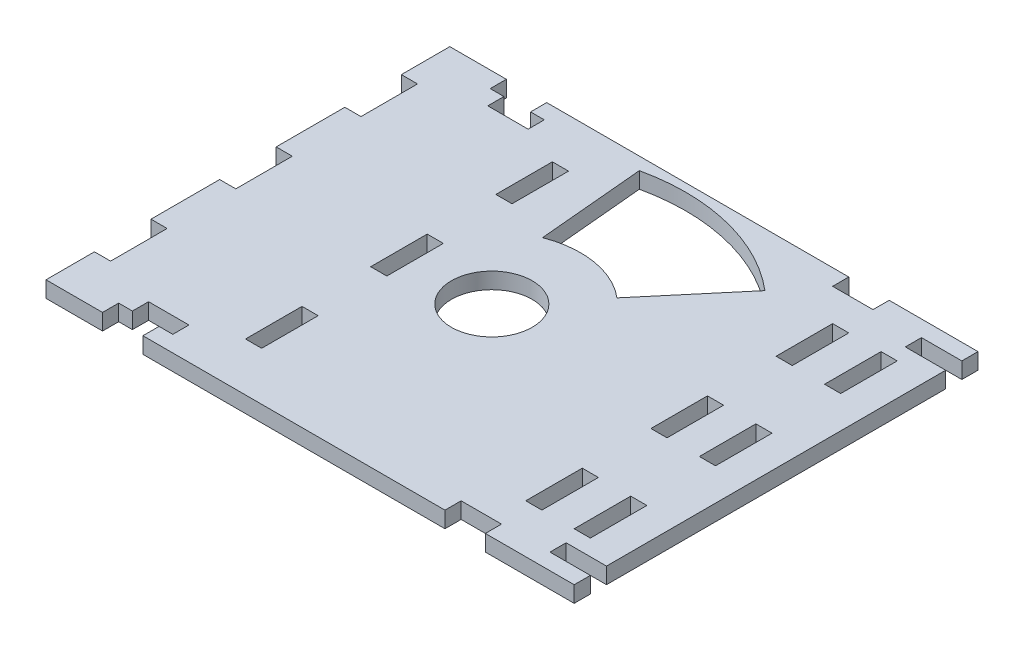
SolidWorks part; units mm, degrees
ref_plane "Front Plane" through (0, 0, 0) normal (0, 0, 1) x (1, 0, 0)
ref_plane "Top Plane" through (0, 0, 0) normal (0, 1, 0) x (1, 0, 0)
ref_plane "Right Plane" through (0, 0, 0) normal (1, 0, 0) x (0, 0, -1)
sketch "Sketch2" plane through (0, 0, 0) normal (0, 1, 0) x (1, 0, 0)
  line L1 (-50, 25) -> (50, 25)
  line L2 (-50, 25) -> (-50, -25)
  line L3 (-50, -25) -> (50, -25)
  line L4 (50, 25) -> (50, -25)
  line L5 (-50, 25) -> (50, -25) construction
  line L6 (-50, -25) -> (50, 25) construction
  circle A0 centre (0, 0) radius 5
  point P0 (0, 0)
  dimension "D3" = 10
  dimension "D1" = 100
  dimension "D2" = 50
extrude "Boss-Extrude1" add sketch "Sketch2" along normal blind 2
sketch "Sketch5" plane through (0, 0, 0) normal (0, -1, 0) x (-1, 0, 0)
  line L0 (-50, 25) -> (50, 25) construction
  line L1 (-23.2, -19) -> (-25.2, -19)
  line L2 (-23.2, -19) -> (-23.2, -12)
  line L3 (-23.2, -12) -> (-25.2, -12)
  line L4 (-25.2, -19) -> (-25.2, -12)
  line L5 (-23.2, -3.5) -> (-25.2, -3.5)
  line L6 (-23.2, -3.5) -> (-23.2, 3.5)
  line L7 (-23.2, 3.5) -> (-25.2, 3.5)
  line L8 (-25.2, -3.5) -> (-25.2, 3.5)
  line L9 (-23.2, 12) -> (-25.2, 12)
  line L10 (-23.2, 12) -> (-23.2, 19)
  line L11 (-23.2, 19) -> (-25.2, 19)
  line L12 (-25.2, 12) -> (-25.2, 19)
  line L13 (11.5, 12) -> (9.5, 12)
  line L14 (11.5, 12) -> (11.5, 19)
  line L15 (11.5, 19) -> (9.5, 19)
  line L16 (9.5, 12) -> (9.5, 19)
  line L17 (11.5, -3.5) -> (9.5, -3.5)
  line L18 (11.5, -3.5) -> (11.5, 3.5)
  line L19 (11.5, 3.5) -> (9.5, 3.5)
  line L20 (9.5, -3.5) -> (9.5, 3.5)
  line L21 (11.5, -19) -> (9.5, -19)
  line L22 (11.5, -19) -> (11.5, -12)
  line L23 (11.5, -12) -> (9.5, -12)
  line L24 (9.5, -19) -> (9.5, -12)
  line L25 (50, -25) -> (-50, -25) construction
  line L26 (-50, 25) -> (50, 25) construction
  line L27 (50, -25) -> (-50, -25) construction
  point P29 (-24.2, -19)
  dimension "D1" = 2
  dimension "D2" = 7
  dimension "D3" = 7
  dimension "D4" = 7
  dimension "D5" = 2
  dimension "D6" = 2
  dimension "D7" = 2
  dimension "D8" = 2
  dimension "D9" = 2
  dimension "D10" = 7
  dimension "D11" = 7
  dimension "D12" = 7
  dimension "D13" = 6
  dimension "D14" = 8.5
  dimension "D15" = 8.5
  dimension "D16" = 6
  dimension "D17" = 6
  dimension "D18" = 8.5
  dimension "D19" = 8.5
  dimension "D20" = 6
  dimension "D21" = 9.5
  dimension "D22" = 0
  dimension "D23" = 32.7
  dimension "D24" = 0
  dimension "D25" = 0
  dimension "D26" = 0
  dimension "D27" = 32.7
extrude "Cut-Extrude3" cut sketch "Sketch5" against normal blind 2
sketch "Sketch10" plane through (0, 2, 0) normal (0, 1, 0) x (1, 0, 0)
  line L0 (-5.1716, 23.4362) -> (-3.9753, 10.2565)
  line L1 (15.4739, 18.3455) -> (7.0922, 8.4084)
  arc A0 (-3.9753, 10.2565) -> (7.0922, 8.4084) centre (0, 0) cw
  arc A1 (-5.1716, 23.4362) -> (15.4739, 18.3455) centre (0, 0) cw
  dimension "D1" = 24
  dimension "D2" = 11
extrude "Cut-Extrude6" cut sketch "Sketch10" against normal blind 2 contours A1 L0 A0 L1 region at (3.832, 2, -17.0402)
sketch "Sketch11" plane through (0, 2, 0) normal (0, 1, 0) x (1, 0, 0)
  line L0 (-50, -25) -> (50, -25) construction
  line L1 (-21.5, -25) -> (-16.5, -25)
  line L2 (-21.5, -25) -> (-21.5, -23)
  line L3 (-21.5, -23) -> (-16.5, -23)
  line L4 (-16.5, -25) -> (-16.5, -23)
  line L5 (50, 25) -> (-50, 25) construction
  line L6 (35.2, -25) -> (30.2, -25)
  line L7 (35.2, -25) -> (35.2, -23)
  line L8 (35.2, -23) -> (30.2, -23)
  line L9 (30.2, -25) -> (30.2, -23)
  line L10 (35.2, 25) -> (30.2, 25)
  line L11 (35.2, 25) -> (35.2, 23)
  line L12 (35.2, 23) -> (30.2, 23)
  line L13 (30.2, 25) -> (30.2, 23)
  line L15 (-21.5, 25) -> (-16.5, 25)
  line L16 (-21.5, 25) -> (-21.5, 23)
  line L17 (-21.5, 23) -> (-16.5, 23)
  line L18 (-16.5, 25) -> (-16.5, 23)
  line L19 (35.2, 23) -> (30.2, 23)
  line L20 (35.2, 23) -> (35.2, 21)
  line L21 (35.2, 21) -> (30.2, 21)
  line L22 (30.2, 23) -> (30.2, 21)
  line L23 (-16.5, 23) -> (-21.5, 23)
  line L24 (-16.5, 23) -> (-16.5, 21)
  line L25 (-16.5, 21) -> (-21.5, 21)
  line L26 (-21.5, 23) -> (-21.5, 21)
  line L27 (-16.5, -23) -> (-21.5, -23)
  line L28 (-16.5, -23) -> (-16.5, -21)
  line L29 (-16.5, -21) -> (-21.5, -21)
  line L30 (-21.5, -23) -> (-21.5, -21)
  line L31 (35.2, -23) -> (30.2, -23)
  line L32 (35.2, -23) -> (35.2, -21)
  line L33 (35.2, -21) -> (30.2, -21)
  line L34 (30.2, -23) -> (30.2, -21)
  dimension "D1" = 2
  dimension "D2" = 2
  dimension "D3" = 2
  dimension "D4" = 2
  dimension "D5" = 5
  dimension "D6" = 5
  dimension "D7" = 5
  dimension "D8" = 5
  dimension "D9" = 5
  dimension "D10" = 5
  dimension "D11" = 5
  dimension "D12" = 5
  dimension "D13" = 2
  dimension "D14" = 2
  dimension "D15" = 2
  dimension "D16" = 2
extrude "Cut-Extrude7" cut sketch "Sketch11" against normal blind 2 contours L12 L22 L21 L20 | L17 L26 L25 L24 | L30 L3 L28 L29 | L34 L8 L32 L33 region at (-19, 2, 22) region at (32.7, 2, 22) region at (32.7, 2, -22) region at (-19, 2, -22)
sketch "Sketch12" plane through (0, 2, 0) normal (0, 1, 0) x (1, 0, 0)
  line L0 (-50, -25) -> (50, -25) construction
  line L1 (-43.5, -25) -> (-50, -25)
  line L2 (-43.5, -25) -> (-43.5, 25)
  line L3 (-43.5, 25) -> (-50, 25)
  line L4 (-50, -25) -> (-50, 25)
  line L5 (-50, -25) -> (50, -25) construction
  line L6 (47.2, -25) -> (50, -25)
  line L7 (47.2, -25) -> (47.2, 25)
  line L8 (47.2, 25) -> (50, 25)
  line L9 (50, -25) -> (50, 25)
  line L11 (35.2, 23) -> (35.2, 21) construction
  line L12 (-21.5, 23) -> (-21.5, 21) construction
  dimension "D1" = 12
  dimension "D2" = 22
extrude "Cut-Extrude8" cut sketch "Sketch12" against normal blind 6
sketch "Sketch13" plane through (0, 2, 0) normal (0, 1, 0) x (1, 0, 0)
  line L0 (35.2, 25) -> (35.2, -25)
  line L1 (-28.2, 19) -> (-30.2, 19)
  line L2 (-28.2, 19) -> (-28.2, 12)
  line L3 (-28.2, 12) -> (-30.2, 12)
  line L4 (-30.2, 19) -> (-30.2, 12)
  line L5 (-28.2, 3.5) -> (-30.2, 3.5)
  line L6 (-28.2, 3.5) -> (-28.2, -3.5)
  line L7 (-28.2, -3.5) -> (-30.2, -3.5)
  line L8 (-30.2, 3.5) -> (-30.2, -3.5)
  line L9 (-28.2, -12) -> (-30.2, -12)
  line L10 (-28.2, -12) -> (-28.2, -19)
  line L11 (-28.2, -19) -> (-30.2, -19)
  line L12 (-30.2, -12) -> (-30.2, -19)
  line L13 (29.2, 19) -> (31.2, 19)
  line L14 (29.2, 19) -> (29.2, 12)
  line L15 (29.2, 12) -> (31.2, 12)
  line L16 (31.2, 19) -> (31.2, 12)
  line L17 (29.2, 3.5) -> (31.2, 3.5)
  line L18 (29.2, 3.5) -> (29.2, -3.5)
  line L19 (29.2, -3.5) -> (31.2, -3.5)
  line L20 (31.2, 3.5) -> (31.2, -3.5)
  line L21 (29.2, -12) -> (31.2, -12)
  line L22 (29.2, -12) -> (29.2, -19)
  line L23 (29.2, -19) -> (31.2, -19)
  line L24 (31.2, -12) -> (31.2, -19)
  line L26 (47.2, 25) -> (-43.5, 25) construction
  line L27 (47.2, 25) -> (-43.5, 25) construction
  line L28 (-43.5, -25) -> (47.2, -25) construction
  line L29 (47.2, 25) -> (-43.5, 25) construction
  line L30 (-43.5, -25) -> (47.2, -25) construction
  line L31 (-43.5, -25) -> (-30.2, -25)
  line L32 (-43.5, -25) -> (-43.5, 25)
  line L33 (-43.5, 25) -> (-30.2, 25)
  line L34 (-30.2, -25) -> (-30.2, 25)
  line L35 (47.2, -25) -> (31.2, -25)
  line L36 (47.2, -25) -> (47.2, 25)
  line L37 (47.2, 25) -> (31.2, 25)
  line L38 (31.2, -25) -> (31.2, 25)
  line L39 (24.2, -25) -> (19.2, -25)
  line L40 (24.2, -25) -> (24.2, -23)
  line L41 (24.2, -23) -> (19.2, -23)
  line L42 (19.2, -25) -> (19.2, -23)
  line L43 (24.2, 23) -> (19.2, 23)
  line L44 (24.2, 23) -> (24.2, 25)
  line L45 (24.2, 25) -> (19.2, 25)
  line L46 (19.2, 23) -> (19.2, 25)
  line L48 (-23.2, 25) -> (-18.2, 25)
  line L49 (-23.2, 25) -> (-23.2, 23)
  line L50 (-23.2, 23) -> (-18.2, 23)
  line L51 (-18.2, 25) -> (-18.2, 23)
  line L52 (-23.2, -25) -> (-18.2, -25)
  line L53 (-23.2, -25) -> (-23.2, -23)
  line L54 (-23.2, -23) -> (-18.2, -23)
  line L55 (-18.2, -25) -> (-18.2, -23)
  point P30 (30.2, 3.5)
  point P47 (28.637, 23.1685)
  line M32 (47.2, -25) -> (47.2, 25)
  line M39 (-21.5, 23) -> (-16.5, 23)
  line M41 (47.2, 25) -> (-43.5, 25)
  line M42 (-43.5, 25) -> (-43.5, -25)
  line M45 (-16.5, -23) -> (-21.5, -23)
  line M47 (-43.5, -25) -> (47.2, -25)
  line M120 (35.2, 23) -> (35.2, 21)
  line M125 (35.2, -21) -> (35.2, -23)
  dimension "D1" = 2
  dimension "D2" = 2
  dimension "D3" = 2
  dimension "D4" = 2
  dimension "D5" = 2
  dimension "D6" = 2
  dimension "D7" = 57.4
  dimension "D8" = 57.4
  dimension "D9" = 57.4
  dimension "D10" = 7
  dimension "D11" = 7
  dimension "D12" = 7
  dimension "D13" = 7
  dimension "D14" = 7
  dimension "D15" = 7
  dimension "D16" = 5
  dimension "D17" = 5
  dimension "D18" = 5
  dimension "D19" = 6
  dimension "D20" = 8.5
  dimension "D21" = 8.5
  dimension "D22" = 6
  dimension "D23" = 6
  dimension "D24" = 8.5
  dimension "D25" = 8.5
  dimension "D26" = 6
  dimension "D27" = 5
  dimension "D28" = 2
  dimension "D29" = 2
  dimension "D30" = 2
  dimension "D31" = 2
  dimension "D32" = 5
  dimension "D33" = 5
  dimension "D34" = 5
  dimension "D35" = 5
extrude "Cut-Extrude10" cut sketch "Sketch13" against normal blind 6 contours L0 M41 M120 M125 M47 M32 | L42 L40 L41 M47 | L24 L21 L22 L23 | L20 L17 L18 L19 | L16 L13 L14 L15 | L51 L49 L50 M41 M39 | L55 L54 L53 M47 M45 | L5 L8 L7 L6 | L1 L4 L3 L2 | L34 L12 L8 L4 M47 M41 M42 | L45 L46 L43 L44 | L10 L11 L12 L9 region at (41.2, 2, 0) region at (30.2, 2, -15.5) region at (30.2, 2, 0) region at (-20.7, 2, -24) region at (30.2, 2, 15.5) region at (21.7, 2, 24) region at (-36.85, 2, 0) region at (-20.7, 2, 24) region at (-29.2, 2, -15.5) region at (-29.2, 2, 0)
